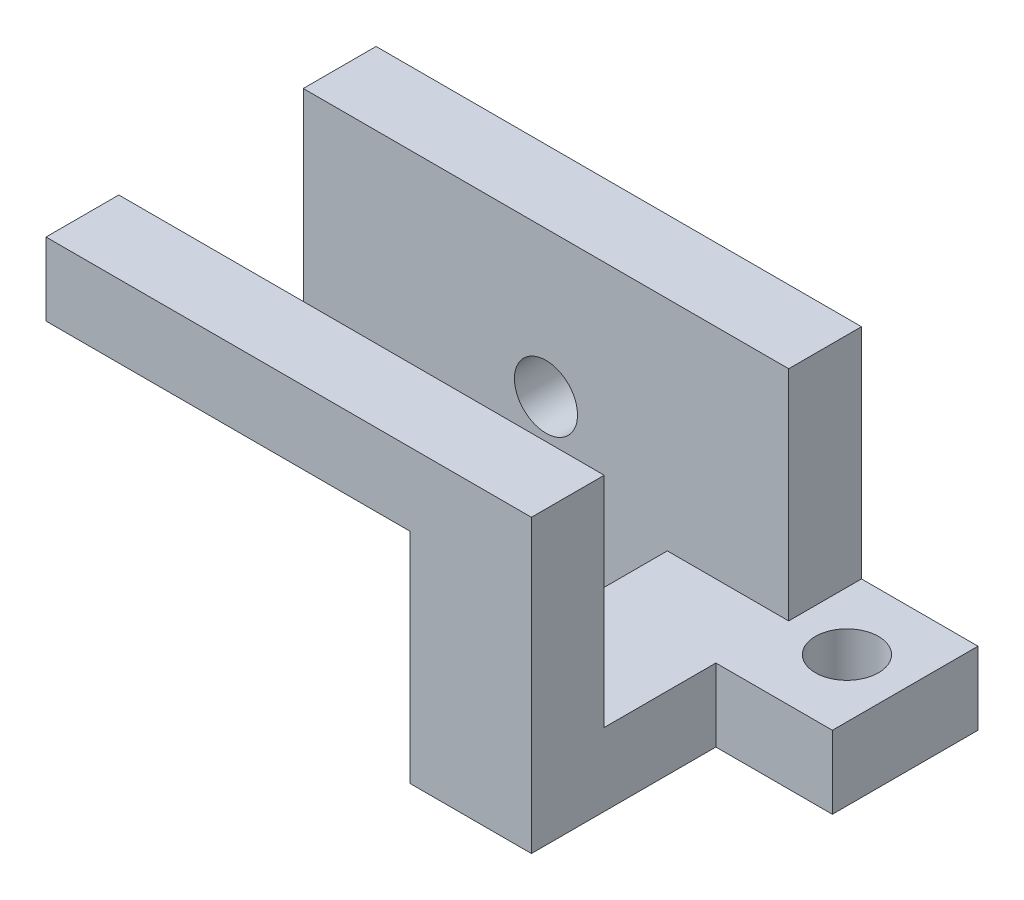
SolidWorks part; units mm, degrees
ref_plane "Front Plane" through (0, 0, 0) normal (0, 0, 1) x (1, 0, 0)
ref_plane "Top Plane" through (0, 0, 0) normal (0, 1, 0) x (1, 0, 0)
ref_plane "Right Plane" through (0, 0, 0) normal (1, 0, 0) x (0, 0, -1)
sketch "Sketch1" plane through (0, 0, 0) normal (0, 0, 1) x (1, 0, 0)
  line L0 (50, -30) -> (74, -30)
  line L1 (-50, -30) -> (50, -30)
  line L2 (-50, -30) -> (-50, 30)
  line L3 (-50, 30) -> (50, 30)
  line L4 (50, -30) -> (50, 30)
  line L5 (-50, -30) -> (50, 30) construction
  line L6 (-50, 30) -> (50, -30) construction
  line L7 (74, -30) -> (74, -15)
  line L8 (74, -15) -> (50, -15)
  point P0 (0, 0)
  dimension "D1" = 100
  dimension "D2" = 60
  dimension "D3" = 24
  dimension "D4" = 15
extrude "Boss-Extrude1" add sketch "Sketch1" along normal blind 68 contours L1 L4 L3 L2 region at (0, 0, 0)
extrude "Boss-Extrude2" add sketch "Sketch1<3>" along normal blind 30 contours L7 L8 L4 L0 region at (62, -22.5, 0)
sketch "Sketch1<3>" plane through (0, 0, 0) normal (0, 0, 1) x (1, 0, 0) same geometry as "Sketch1"
sketch "Sketch2" plane through (0, -15, 0) normal (0, 1, 0) x (1, 0, 0)
  circle A0 centre (62, -15) radius 6.5
extrude "Cut-Extrude1" cut sketch "Sketch2" against normal blind 40
sketch "Sketch3" plane through (50, 0, 0) normal (1, 0, 0) x (0, 0, -1)
  line L0 (-15, 30) -> (-15, -15)
  line L1 (-68, 30) -> (0, 30) construction
  line L2 (-30, -15) -> (0, -15) construction
  line L3 (0, -15) -> (0, 30) construction
  line L4 (-53, -15) -> (-53, 30)
  line L5 (-68, -30) -> (-68, 30) construction
  line L6 (-15, -15) -> (-53, -15)
  line L7 (-15, 30) -> (-53, 30)
  dimension "D1" = 15
  dimension "D2" = 15
extrude "Cut-Extrude2" cut sketch "Sketch3" against normal blind 113 contours L0 L6 L4 L7
sketch "Sketch4" plane through (0, 0, 68) normal (0, 0, 1) x (1, 0, 0)
  line L0 (25, -30) -> (25, 15)
  line L1 (-50, -30) -> (50, -30) construction
  line L2 (25, 15) -> (-50, 15)
  line L3 (-50, -30) -> (-50, 30) construction
  point P4 (0, 0)
  line M3 (-50, -30) -> (50, -30)
  line M6 (-50, 30) -> (-50, -30)
  dimension "D1" = 75
  dimension "D2" = 45
extrude "Cut-Extrude3" cut sketch "Sketch4" against normal blind 53 and the other way through all contours L0 L2 M6 M3 region at (-12.5, -7.5, 68)
sketch "Sketch5" plane through (0, 0, 0) normal (0, 0, -1) x (-1, 0, 0)
  circle A0 centre (0, 0) radius 6.5
extrude "Cut-Extrude4" cut sketch "Sketch5" against normal blind 38
